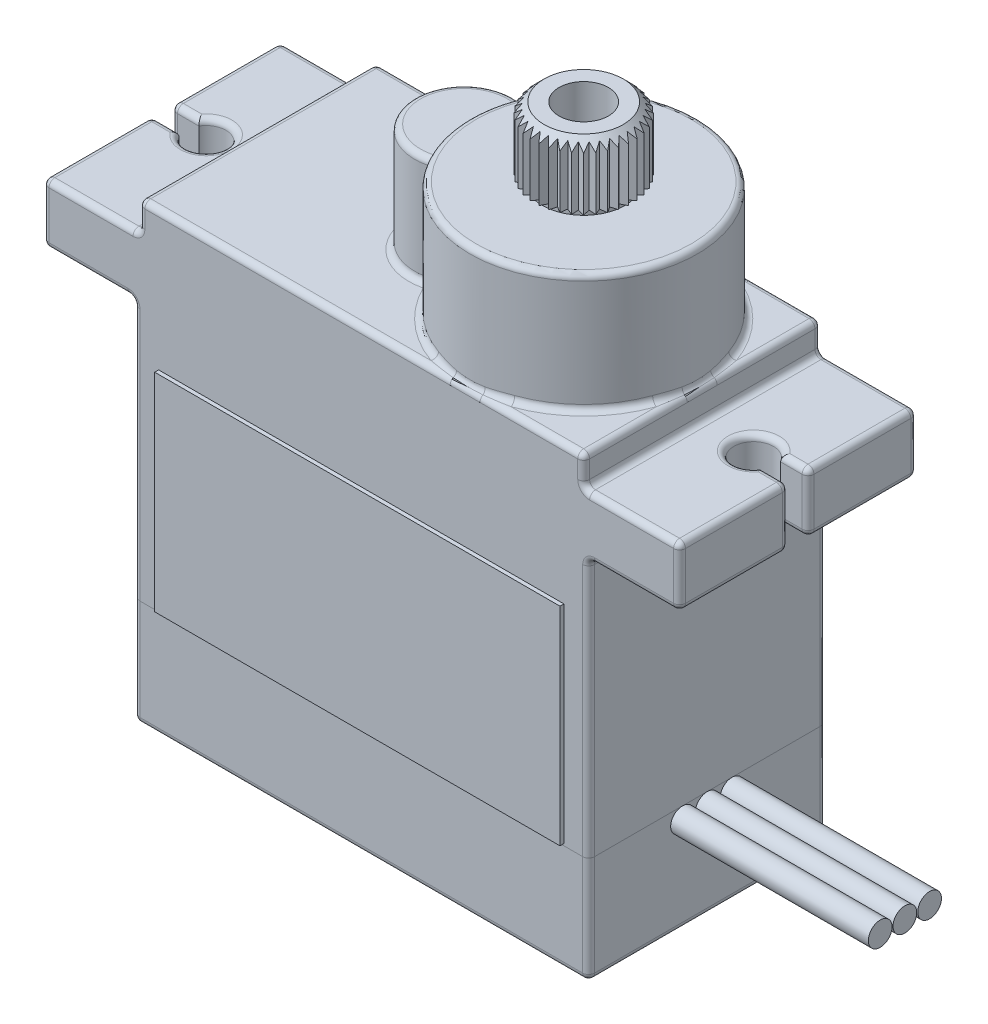
SolidWorks part; units mm, degrees
ref_plane "Front Plane" through (0, 0, 0) normal (0, 0, 1) x (1, 0, 0)
ref_plane "Top Plane" through (0, 0, 0) normal (0, 1, 0) x (1, 0, 0)
ref_plane "Right Plane" through (0, 0, 0) normal (1, 0, 0) x (0, 0, -1)
sketch "Sketch1" plane through (0, 0, 0) normal (0, 1, 0) x (1, 0, 0)
  line L1 (-11.5, -6) -> (11.5, -6)
  line L2 (-11.5, -6) -> (-11.5, 6)
  line L3 (-11.5, 6) -> (11.5, 6)
  line L4 (11.5, -6) -> (11.5, 6)
  line L5 (-11.5, -6) -> (11.5, 6) construction
  line L6 (-11.5, 6) -> (11.5, -6) construction
  point P0 (0, 0)
  dimension "D1" = 12
  dimension "D2" = 23
extrude "Boss-Extrude1" add sketch "Sketch1" along normal blind 18.5
sketch "Sketch2" plane through (0, 18.5, 0) normal (0, 1, 0) x (1, 0, 0)
  line L0 (11.5, 6) -> (-11.5, 6) construction
  line L1 (-16.1, -6) -> (16.1, -6)
  line L2 (-16.1, -6) -> (-16.1, 6)
  line L3 (-16.1, 6) -> (16.1, 6)
  line L4 (16.1, -6) -> (16.1, 6)
  line L5 (-16.1, -6) -> (16.1, 6) construction
  line L6 (-16.1, 6) -> (16.1, -6) construction
  point P0 (0, 0)
  dimension "D1" = 32.2
extrude "Boss-Extrude2" add sketch "Sketch2" along normal blind 3
sketch "Sketch3" plane through (0, 21.5, 0) normal (0, 1, 0) x (1, 0, 0)
  line L0 (16.1, 6) -> (-16.1, 6) construction
  line L1 (-11.25, -6) -> (11.25, -6)
  line L2 (-11.25, -6) -> (-11.25, 6)
  line L3 (-11.25, 6) -> (11.25, 6)
  line L4 (11.25, -6) -> (11.25, 6)
  line L5 (-11.25, -6) -> (11.25, 6) construction
  line L6 (-11.25, 6) -> (11.25, -6) construction
  point P0 (0, 0)
  dimension "D1" = 22.5
extrude "Boss-Extrude3" add sketch "Sketch3" along normal blind 1.5
sketch "Sketch4" plane through (0, 23, 0) normal (0, 1, 0) x (1, 0, 0)
  line L0 (-11.25, 6) -> (-11.25, -6) construction
  line L1 (5.25, 5.75) -> (5.25, 6) construction
  line L2 (11.25, 6) -> (-11.25, 6) construction
  line L3 (11, 0) -> (11.25, 0) construction
  line L4 (11.25, -6) -> (11.25, 6) construction
  line L5 (5.25, -5.75) -> (5.25, -6) construction
  line L6 (-11.25, -6) -> (11.25, -6) construction
  circle A0 centre (5.25, 0) radius 5.75
  point P5 (-11.25, 0)
  dimension "D1" = 11.5
extrude "Boss-Extrude4" add sketch "Sketch4" along normal blind 6
sketch "Sketch5" plane through (0, 23, 0) normal (0, 1, 0) x (1, 0, 0)
  line L0 (-11.25, 6) -> (-11.25, -6) construction
  circle A0 centre (-0.8, 0) radius 2.5
  circle A1 centre (5.25, 0) radius 5.75 construction
  circle A2 centre (5.25, 0) radius 5.75 construction
  point P2 (-3.3, 0)
  point P5 (-11.25, 0)
  point P6 (11, 0)
  dimension "D1" = 5
  dimension "D2" = 14.3
extrude "Boss-Extrude5" add sketch "Sketch5" along normal blind 5.5
sketch "Sketch6" plane through (0, 21.5, 0) normal (0, 1, 0) x (1, 0, 0)
  line L0 (-11.25, 6) -> (-11.25, -6) construction
  line L1 (0, 6) -> (0, -6) construction
  line L2 (11.25, 6) -> (-11.25, 6) construction
  line L3 (-11.25, -6) -> (11.25, -6) construction
  line L4 (-14.716, 0.5) -> (-16.1, 0.5)
  line L5 (-16.1, 6) -> (-16.1, -6) construction
  line L6 (-14.716, -0.5) -> (-16.1, -0.5)
  line L7 (-16.1, 0.5) -> (-16.1, -0.5)
  line L8 (16.1, 0.5) -> (16.1, -0.5)
  line L9 (14.716, -0.5) -> (16.1, -0.5)
  line L10 (14.716, 0.5) -> (16.1, 0.5)
  arc A0 (-14.716, -0.5) -> (-14.716, 0.5) centre (-13.85, 0) ccw
  arc A1 (14.716, -0.5) -> (14.716, 0.5) centre (13.85, 0) cw
  point P4 (-11.25, 0)
  dimension "D1" = 2
  dimension "D2" = 27.7
  dimension "D3" = 1
extrude "Cut-Extrude1" cut sketch "Sketch6" against normal through all
sketch "Sketch7" plane through (0, 29, 0) normal (0, 1, 0) x (1, 0, 0)
  circle A0 centre (5.25, 0) radius 2.5
  dimension "D1" = 5
extrude "Boss-Extrude6" add sketch "Sketch7" along normal blind 3.5
sketch "Sketch8" plane through (11.5, 0, 0) normal (1, 0, 0) x (0, 0, -1)
  line L0 (-1.25, 4.8) -> (1.25, 4.8) construction
  line L1 (-6, 0) -> (6, 0) construction
  circle A0 centre (-1.25, 4.8) radius 0.6
  circle A1 centre (0, 4.8) radius 0.6
  circle A2 centre (1.25, 4.8) radius 0.6
  dimension "D1" = 1.2
  dimension "D2" = 4.8
  dimension "D3" = 2.5
extrude "Boss-Extrude8" add sketch "Sketch8" along normal blind 10
fillet "Fillet1" radius 0.3 56 edges at (11.5, 0, 0) (11.5, 18.5, 0) (15.408, 18.5, 0.5) (12.85, 18.5, 0) (15.408, 18.5, -0.5) (15.408, 21.5, 0.5) (15.408, 21.5, -0.5) (12.85, 21.5, 0) (-11.25, 23, 0) (-15.408, 21.5, -0.5) (-11.25, 21.5, 0) (-15.408, 21.5, 0.5) (-12.85, 21.5, 0) (-16.1, 20, 0.5) (-16.1, 21.5, 3.25) (-16.1, 21.5, -3.25) (-16.1, 20, -0.5) (-16.1, 18.5, 3.25) (-16.1, 18.5, -3.25) (-15.408, 18.5, -0.5) (-12.85, 18.5, 0) (-15.408, 18.5, 0.5) (-11.5, 18.5, 0) (-11.5, 0, 0) (11.25, 23, 0) (11.25, 21.5, 0) (16.1, 21.5, 3.25) (16.1, 20, 0.5) (16.1, 18.5, 3.25) (16.1, 18.5, -3.25) (16.1, 20, -0.5) (16.1, 21.5, -3.25) (11.5, 9.25, -6) (13.8, 18.5, -6) (16.1, 20, -6) (13.675, 21.5, -6) (11.25, 22.25, -6) (0, 23, -6) (-11.25, 22.25, -6) (-13.675, 21.5, -6) (-16.1, 20, -6) (-13.8, 18.5, -6) (-11.5, 9.25, -6) (0, 0, -6) (-11.5, 9.25, 6) (-13.8, 18.5, 6) (-16.1, 20, 6) (-13.675, 21.5, 6) (-11.25, 22.25, 6) (0, 23, 6) (11.25, 22.25, 6) (13.675, 21.5, 6) (16.1, 20, 6) (13.8, 18.5, 6) (11.5, 9.25, 6) (0, 0, 6)
fillet "Fillet2" radius 0.3 10 edges at (5.25, 23, 5.75) (9.3159, 23, 4.0659) (11, 23, 0) (9.3159, 23, -4.0659) (5.25, 23, -5.75) (-3.3, 23, 0) (1.8189, 23, 4.6141) (1.8189, 23, -4.6141) (5.25, 29, 5.75) (-3.3, 28.5, 0)
chamfer "Chamfer1" distance 0.5 angle 45 1 edges at (5.25, 32.5, 2.5)
sketch "Sketch10" plane through (0, 32.5, 0) normal (0, 1, 0) x (1, 0, 0)
  line L0 (5.25, 0) -> (5.0321, 2.4905) construction
  line L1 (5.25, 0) -> (5.4679, 2.4905) construction
  line L2 (5.25, 0) -> (5.25, 2.5) construction
  line L3 (5.0321, 2.4905) -> (5.25, 2.2)
  line L4 (5.25, 2.2) -> (5.4679, 2.4905)
  line L5 (5.632, 2.1666) -> (5.897, 2.4148)
  line L6 (5.4679, 2.4905) -> (5.632, 2.1666)
  line L7 (6.0024, 2.0673) -> (6.3065, 2.2658)
  line L8 (5.897, 2.4148) -> (6.0024, 2.0673)
  line L9 (6.35, 1.9053) -> (6.6839, 2.0479)
  line L10 (6.3065, 2.2658) -> (6.35, 1.9053)
  line L11 (6.6641, 1.6853) -> (7.0178, 1.7678)
  line L12 (6.6839, 2.0479) -> (6.6641, 1.6853)
  line L13 (6.9353, 1.4141) -> (7.2979, 1.4339)
  line L14 (7.0178, 1.7678) -> (6.9353, 1.4141)
  line L15 (7.1553, 1.1) -> (7.5158, 1.0565)
  line L16 (7.2979, 1.4339) -> (7.1553, 1.1)
  line L17 (7.3173, 0.7524) -> (7.6648, 0.647)
  line L18 (7.5158, 1.0565) -> (7.3173, 0.7524)
  line L19 (7.4166, 0.382) -> (7.7405, 0.2179)
  line L20 (7.6648, 0.647) -> (7.4166, 0.382)
  line L21 (7.45, 0) -> (7.7405, -0.2179)
  line L22 (7.7405, 0.2179) -> (7.45, 0)
  line L23 (7.4166, -0.382) -> (7.6648, -0.647)
  line L24 (7.7405, -0.2179) -> (7.4166, -0.382)
  line L25 (7.3173, -0.7524) -> (7.5158, -1.0565)
  line L26 (7.6648, -0.647) -> (7.3173, -0.7524)
  line L27 (7.1553, -1.1) -> (7.2979, -1.4339)
  line L28 (7.5158, -1.0565) -> (7.1553, -1.1)
  line L29 (6.9353, -1.4141) -> (7.0178, -1.7678)
  line L30 (7.2979, -1.4339) -> (6.9353, -1.4141)
  line L31 (6.6641, -1.6853) -> (6.6839, -2.0479)
  line L32 (7.0178, -1.7678) -> (6.6641, -1.6853)
  line L33 (6.35, -1.9053) -> (6.3065, -2.2658)
  line L34 (6.6839, -2.0479) -> (6.35, -1.9053)
  line L35 (6.0024, -2.0673) -> (5.897, -2.4148)
  line L36 (6.3065, -2.2658) -> (6.0024, -2.0673)
  line L37 (5.632, -2.1666) -> (5.4679, -2.4905)
  line L38 (5.897, -2.4148) -> (5.632, -2.1666)
  line L39 (5.25, -2.2) -> (5.0321, -2.4905)
  line L40 (5.4679, -2.4905) -> (5.25, -2.2)
  line L41 (4.868, -2.1666) -> (4.603, -2.4148)
  line L42 (5.0321, -2.4905) -> (4.868, -2.1666)
  line L43 (4.4976, -2.0673) -> (4.1935, -2.2658)
  line L44 (4.603, -2.4148) -> (4.4976, -2.0673)
  line L45 (4.15, -1.9053) -> (3.8161, -2.0479)
  line L46 (4.1935, -2.2658) -> (4.15, -1.9053)
  line L47 (3.8359, -1.6853) -> (3.4822, -1.7678)
  line L48 (3.8161, -2.0479) -> (3.8359, -1.6853)
  line L49 (3.5647, -1.4141) -> (3.2021, -1.4339)
  line L50 (3.4822, -1.7678) -> (3.5647, -1.4141)
  line L51 (3.3447, -1.1) -> (2.9842, -1.0565)
  line L52 (3.2021, -1.4339) -> (3.3447, -1.1)
  line L53 (3.1827, -0.7524) -> (2.8352, -0.647)
  line L54 (2.9842, -1.0565) -> (3.1827, -0.7524)
  line L55 (3.0834, -0.382) -> (2.7595, -0.2179)
  line L56 (2.8352, -0.647) -> (3.0834, -0.382)
  line L57 (3.05, 0) -> (2.7595, 0.2179)
  line L58 (2.7595, -0.2179) -> (3.05, 0)
  line L59 (3.0834, 0.382) -> (2.8352, 0.647)
  line L60 (2.7595, 0.2179) -> (3.0834, 0.382)
  line L61 (3.1827, 0.7524) -> (2.9842, 1.0565)
  line L62 (2.8352, 0.647) -> (3.1827, 0.7524)
  line L63 (3.3447, 1.1) -> (3.2021, 1.4339)
  line L64 (2.9842, 1.0565) -> (3.3447, 1.1)
  line L65 (3.5647, 1.4141) -> (3.4822, 1.7678)
  line L66 (3.2021, 1.4339) -> (3.5647, 1.4141)
  line L67 (3.8359, 1.6853) -> (3.8161, 2.0479)
  line L68 (3.4822, 1.7678) -> (3.8359, 1.6853)
  line L69 (4.15, 1.9053) -> (4.1935, 2.2658)
  line L70 (3.8161, 2.0479) -> (4.15, 1.9053)
  line L71 (4.4976, 2.0673) -> (4.603, 2.4148)
  line L72 (4.1935, 2.2658) -> (4.4976, 2.0673)
  line L73 (4.868, 2.1666) -> (5.0321, 2.4905)
  line L74 (4.603, 2.4148) -> (4.868, 2.1666)
  circle A0 centre (5.25, 0) radius 2.5 construction
  arc A1 (5.4679, 2.4905) -> (5.0321, 2.4905) centre (5.25, 0) ccw
  circle A2 centre (5.25, 0) radius 2.2 construction
  arc A3 (5.897, 2.4148) -> (5.4679, 2.4905) centre (5.25, 0) ccw
  arc A4 (6.3065, 2.2658) -> (5.897, 2.4148) centre (5.25, 0) ccw
  arc A5 (6.6839, 2.0479) -> (6.3065, 2.2658) centre (5.25, 0) ccw
  arc A6 (7.0178, 1.7678) -> (6.6839, 2.0479) centre (5.25, 0) ccw
  arc A7 (7.2979, 1.4339) -> (7.0178, 1.7678) centre (5.25, 0) ccw
  arc A8 (7.5158, 1.0565) -> (7.2979, 1.4339) centre (5.25, 0) ccw
  arc A9 (7.6648, 0.647) -> (7.5158, 1.0565) centre (5.25, 0) ccw
  arc A10 (7.7405, 0.2179) -> (7.6648, 0.647) centre (5.25, 0) ccw
  arc A11 (7.7405, -0.2179) -> (7.7405, 0.2179) centre (5.25, 0) ccw
  arc A12 (7.6648, -0.647) -> (7.7405, -0.2179) centre (5.25, 0) ccw
  arc A13 (7.5158, -1.0565) -> (7.6648, -0.647) centre (5.25, 0) ccw
  arc A14 (7.2979, -1.4339) -> (7.5158, -1.0565) centre (5.25, 0) ccw
  arc A15 (7.0178, -1.7678) -> (7.2979, -1.4339) centre (5.25, 0) ccw
  arc A16 (6.6839, -2.0479) -> (7.0178, -1.7678) centre (5.25, 0) ccw
  arc A17 (6.3065, -2.2658) -> (6.6839, -2.0479) centre (5.25, 0) ccw
  arc A18 (5.897, -2.4148) -> (6.3065, -2.2658) centre (5.25, 0) ccw
  arc A19 (5.4679, -2.4905) -> (5.897, -2.4148) centre (5.25, 0) ccw
  arc A20 (5.0321, -2.4905) -> (5.4679, -2.4905) centre (5.25, 0) ccw
  arc A21 (4.603, -2.4148) -> (5.0321, -2.4905) centre (5.25, 0) ccw
  arc A22 (4.1935, -2.2658) -> (4.603, -2.4148) centre (5.25, 0) ccw
  arc A23 (3.8161, -2.0479) -> (4.1935, -2.2658) centre (5.25, 0) ccw
  arc A24 (3.4822, -1.7678) -> (3.8161, -2.0479) centre (5.25, 0) ccw
  arc A25 (3.2021, -1.4339) -> (3.4822, -1.7678) centre (5.25, 0) ccw
  arc A26 (2.9842, -1.0565) -> (3.2021, -1.4339) centre (5.25, 0) ccw
  arc A27 (2.8352, -0.647) -> (2.9842, -1.0565) centre (5.25, 0) ccw
  arc A28 (2.7595, -0.2179) -> (2.8352, -0.647) centre (5.25, 0) ccw
  arc A29 (2.7595, 0.2179) -> (2.7595, -0.2179) centre (5.25, 0) ccw
  arc A30 (2.8352, 0.647) -> (2.7595, 0.2179) centre (5.25, 0) ccw
  arc A31 (2.9842, 1.0565) -> (2.8352, 0.647) centre (5.25, 0) ccw
  arc A32 (3.2021, 1.4339) -> (2.9842, 1.0565) centre (5.25, 0) ccw
  arc A33 (3.4822, 1.7678) -> (3.2021, 1.4339) centre (5.25, 0) ccw
  arc A34 (3.8161, 2.0479) -> (3.4822, 1.7678) centre (5.25, 0) ccw
  arc A35 (4.1935, 2.2658) -> (3.8161, 2.0479) centre (5.25, 0) ccw
  arc A36 (4.603, 2.4148) -> (4.1935, 2.2658) centre (5.25, 0) ccw
  arc A37 (5.0321, 2.4905) -> (4.603, 2.4148) centre (5.25, 0) ccw
  point P114 (5.25, 0)
  dimension "D1" = 4.4
  dimension "D2" = 10
  dimension "D3" = 36
extrude "Cut-Extrude2" cut sketch "Sketch10" against normal up to surface (3.5 mm away) contours L69 A35 L70 | L67 A34 L68 | L65 A33 L66 | L63 A32 L64 | L61 A31 L62 | L59 A30 L60 | L57 A29 L58 | L55 A28 L56 | L53 A27 L54 | L51 A26 L52 | L49 A25 L50 | L45 A23 L46 | L43 A22 L44 | L41 A21 L42 | L39 A20 L40 | L37 A19 L38 | L35 A18 L36 | L33 A17 L34 | L31 A16 L32 | L29 A15 L30 | L27 A14 L28 | L25 A13 L26 | L23 A12 L24 | L21 A11 L22 | L19 A10 L20 | L17 A9 L18 | L15 A8 L16 | L13 A7 L14 | L11 A6 L12 | L9 A5 L10 | L7 A4 L8 | L5 A3 L6 | L4 A1 L3 | L73 A37 L74 | L71 A36 L72 | L47 A24 L48 region at (5.25, 32.5, -2.3979) region at (4.8336, 32.5, -2.3614) region at (5.6664, 32.5, -2.3614) region at (4.4299, 32.5, -2.2533) region at (6.0701, 32.5, -2.2533) region at (4.0511, 32.5, -2.0766) region at (6.4489, 32.5, -2.0766) region at (3.7087, 32.5, -1.8369) region at (6.7913, 32.5, -1.8369) region at (3.4131, 32.5, -1.5413) region at (7.0869, 32.5, -1.5413) region at (3.1734, 32.5, -1.1989) region at (7.3266, 32.5, -1.1989) region at (2.9967, 32.5, -0.8201) region at (7.5033, 32.5, -0.8201) region at (2.8886, 32.5, -0.4164) region at (7.6114, 32.5, -0.4164) region at (2.8521, 32.5, 0) region at (7.6479, 32.5, 0) region at (2.8886, 32.5, 0.4164) region at (7.6114, 32.5, 0.4164) region at (2.9967, 32.5, 0.8201) region at (7.5033, 32.5, 0.8201) region at (3.1734, 32.5, 1.1989) region at (7.3266, 32.5, 1.1989) region at (3.4131, 32.5, 1.5413) region at (7.0869, 32.5, 1.5413) region at (6.7913, 32.5, 1.8369) region at (4.0511, 32.5, 2.0766) region at (6.4489, 32.5, 2.0766) region at (4.4299, 32.5, 2.2533) region at (6.0701, 32.5, 2.2533) region at (4.8336, 32.5, 2.3614) region at (5.6664, 32.5, 2.3614) region at (5.25, 32.5, 2.3979) up to face at (5.25, 29, 5.45)
sketch "Sketch11" plane through (0, 0, 0) normal (0, 0, 1) x (1, 0, 0)
  line L0 (5.25, 32.5) -> (5.25, 27.5426) construction
  line L1 (7.9405, 29) -> (7.3405, 29)
  line L2 (7.9405, 29) -> (7.9405, 29.3)
  line L3 (7.9405, 29.3) -> (7.3405, 29.3)
  line L4 (7.3405, 29) -> (7.3405, 29.3)
  line L5 (7.25, 32.5) -> (3.25, 32.5) construction
  line L7 (10.7, 29) -> (-0.2, 29) construction
  line L8 (7.7405, 29) -> (7.7405, 32) construction
  dimension "D1" = 0.3
  dimension "D2" = 0.4
  dimension "D3" = 0.2
revolve "Cut-Revolve1" cut sketch "Sketch11" angle 360 about L0
sketch "Sketch12" plane through (0, 0, 6) normal (0, 0, 1) x (1, 0, 0)
  line L0 (11.2, 0) -> (-11.2, 0) construction
  line L1 (-10.25, 5.5) -> (10.25, 5.5)
  line L2 (-10.25, 5.5) -> (-10.25, 16)
  line L3 (-10.25, 16) -> (10.25, 16)
  line L4 (10.25, 5.5) -> (10.25, 16)
  line L5 (-10.25, 5.5) -> (10.25, 16) construction
  line L6 (-10.25, 16) -> (10.25, 5.5) construction
  point P0 (0, 10.75)
  dimension "D1" = 10.5
  dimension "D2" = 20.5
  dimension "D3" = 5.5
extrude "Boss-Extrude9" add sketch "Sketch12" along normal blind 0.2
sketch "Sketch13" plane through (0, 0, -6) normal (0, 0, -1) x (-1, 0, 0)
  line L4 (-10.25, 16) -> (-10.25, 5.5)
  line L5 (10.25, 16) -> (-10.25, 16)
  line L6 (10.25, 5.5) -> (10.25, 16)
  line L7 (-10.25, 5.5) -> (10.25, 5.5)
  line L8 (-10.25, 16) -> (-10.25, 5.5)
  line L9 (10.25, 16) -> (-10.25, 16)
  line L10 (10.25, 5.5) -> (10.25, 16)
  line L11 (-10.25, 5.5) -> (10.25, 5.5)
  dimension "D1" = 0
extrude "Boss-Extrude10" add sketch "Sketch13" along normal blind 0.2
ref_plane "Plane1" through (0, 5.4, 0) normal (0, 1, 0) x (1, 0, 0)
split line "Split Line1"
sketch "Sketch14" plane through (0, 32.5, 0) normal (0, 1, 0) x (1, 0, 0)
  circle A0 centre (5.25, 0) radius 1.25
  dimension "D1" = 2.5
extrude "Cut-Extrude3" cut sketch "Sketch14" against normal blind 2.5
